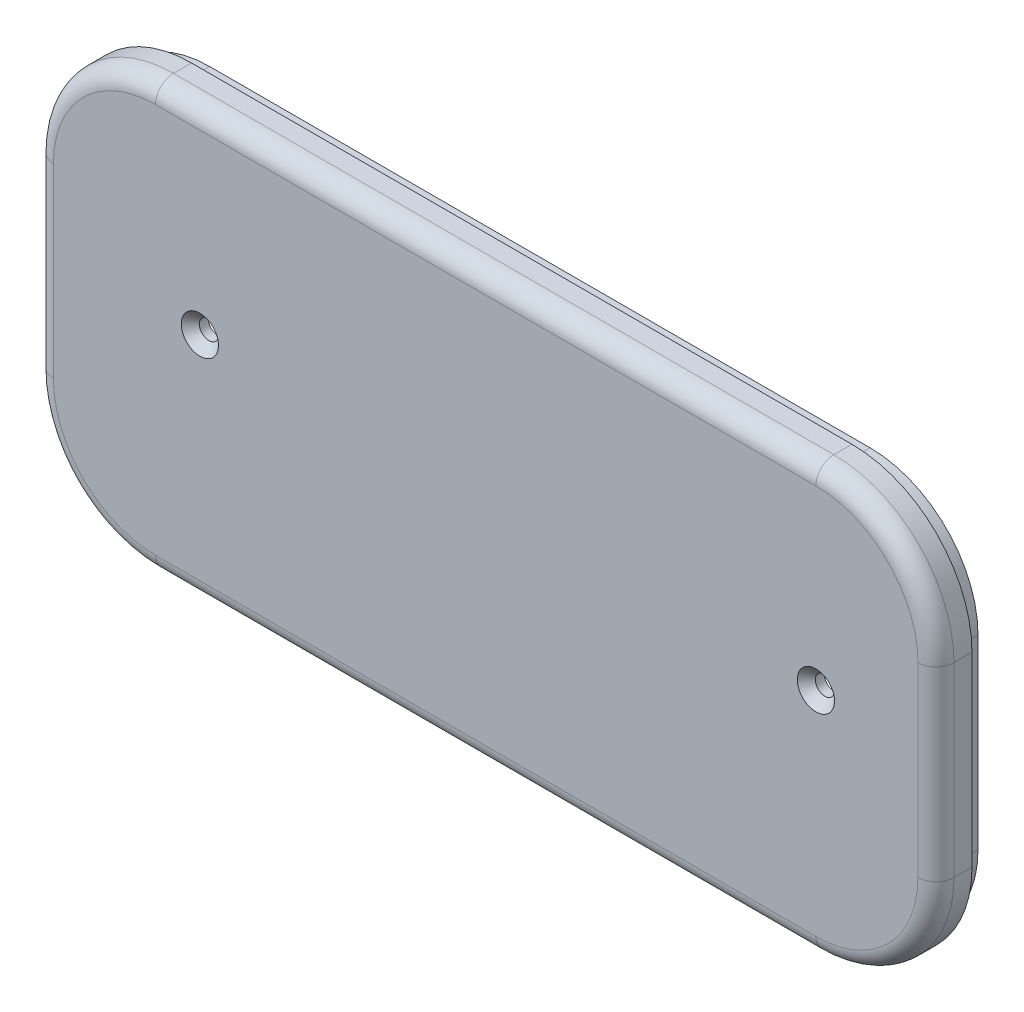
SolidWorks part; units mm, degrees
ref_plane "Front Plane" through (0, 0, 0) normal (0, 0, 1) x (1, 0, 0)
ref_plane "Top Plane" through (0, 0, 0) normal (0, 1, 0) x (1, 0, 0)
ref_plane "Right Plane" through (0, 0, 0) normal (1, 0, 0) x (0, 0, -1)
sketch "Sketch1" plane through (0, 0, 0) normal (0, 0, 1) x (1, 0, 0)
  line L8 (67.5, -46) -> (67.5, -15)
  line L9 (47.5, 5) -> (-62.5, 5)
  line L10 (-82.5, -15) -> (-82.5, -46)
  line L11 (-62.5, -66) -> (47.5, -66)
  arc A8 (47.5, -66) -> (67.5, -46) centre (47.5, -46) ccw
  arc A9 (67.5, -15) -> (47.5, 5) centre (47.5, -15) ccw
  arc A10 (-62.5, 5) -> (-82.5, -15) centre (-62.5, -15) ccw
  arc A11 (-82.5, -46) -> (-62.5, -66) centre (-62.5, -46) ccw
extrude "Boss-Extrude1" add sketch "Sketch1" along normal blind 3
sketch "Sketch2" plane through (0, 0, 0) normal (0, 0, -1) x (-1, 0, 0)
  line L0 (-47.5, -64) -> (62.5, -64)
  line L1 (80.5, -46) -> (80.5, -15)
  line L2 (62.5, 3) -> (-47.5, 3)
  line L3 (-65.5, -15) -> (-65.5, -46)
  line L4 (-47.5, -66) -> (62.5, -66)
  line L5 (82.5, -46) -> (82.5, -15)
  line L6 (62.5, 5) -> (-47.5, 5)
  line L7 (-67.5, -15) -> (-67.5, -46)
  line L8 (-47.5, -66) -> (62.5, -66)
  line L9 (82.5, -46) -> (82.5, -15)
  line L10 (62.5, 5) -> (-47.5, 5)
  line L11 (-67.5, -15) -> (-67.5, -46)
  arc A0 (62.5, -64) -> (80.5, -46) centre (62.5, -46) ccw
  arc A1 (80.5, -15) -> (62.5, 3) centre (62.5, -15) ccw
  arc A2 (-47.5, 3) -> (-65.5, -15) centre (-47.5, -15) ccw
  arc A3 (-65.5, -46) -> (-47.5, -64) centre (-47.5, -46) ccw
  arc A4 (-67.5, -46) -> (-47.5, -66) centre (-47.5, -46) ccw
  arc A5 (62.5, -66) -> (82.5, -46) centre (62.5, -46) ccw
  arc A6 (82.5, -15) -> (62.5, 5) centre (62.5, -15) ccw
  arc A7 (-47.5, 5) -> (-67.5, -15) centre (-47.5, -15) ccw
  arc A8 (-67.5, -46) -> (-47.5, -66) centre (-47.5, -46) ccw
  arc A9 (62.5, -66) -> (82.5, -46) centre (62.5, -46) ccw
  arc A10 (82.5, -15) -> (62.5, 5) centre (62.5, -15) ccw
  arc A11 (-47.5, 5) -> (-67.5, -15) centre (-47.5, -15) ccw
  dimension "D1" = 0
  dimension "D2" = 2
extrude "Boss-Extrude2" add sketch "Sketch2" along normal blind 3
fillet "Fillet1" radius 3 8 edges at (-7.5, -66, 3) (-76.6421, -60.1421, 3) (-82.5, -30.5, 3) (-76.6421, -0.8579, 3) (-7.5, 5, 3) (61.6421, -0.8579, 3) (67.5, -30.5, 3) (61.6421, -60.1421, 3)
sketch "Sketch3" plane through (0, 0, 0) normal (0, 0, -1) x (-1, 0, 0)
  line L0 (-62.5, -15) -> (-62.5, -46)
  line L1 (-47.5, -61) -> (62.5, -61)
  line L2 (77.5, -46) -> (77.5, -15)
  line L3 (62.5, 0) -> (-47.5, 0)
  line L4 (-65.5, -15) -> (-65.5, -46)
  line L5 (-47.5, -64) -> (62.5, -64)
  line L6 (80.5, -46) -> (80.5, -15)
  line L7 (62.5, 3) -> (-47.5, 3)
  line L8 (-65.5, -15) -> (-65.5, -46)
  line L9 (-47.5, -64) -> (62.5, -64)
  line L10 (80.5, -46) -> (80.5, -15)
  line L11 (62.5, 3) -> (-47.5, 3)
  arc A0 (-62.5, -46) -> (-47.5, -61) centre (-47.5, -46) ccw
  arc A1 (62.5, -61) -> (77.5, -46) centre (62.5, -46) ccw
  arc A2 (77.5, -15) -> (62.5, 0) centre (62.5, -15) ccw
  arc A3 (-47.5, 0) -> (-62.5, -15) centre (-47.5, -15) ccw
  arc A4 (-65.5, -46) -> (-47.5, -64) centre (-47.5, -46) ccw
  arc A5 (62.5, -64) -> (80.5, -46) centre (62.5, -46) ccw
  arc A6 (80.5, -15) -> (62.5, 3) centre (62.5, -15) ccw
  arc A7 (-47.5, 3) -> (-65.5, -15) centre (-47.5, -15) ccw
  arc A8 (-65.5, -46) -> (-47.5, -64) centre (-47.5, -46) ccw
  arc A9 (62.5, -64) -> (80.5, -46) centre (62.5, -46) ccw
  arc A10 (80.5, -15) -> (62.5, 3) centre (62.5, -15) ccw
  arc A11 (-47.5, 3) -> (-65.5, -15) centre (-47.5, -15) ccw
  dimension "D1" = 0
  dimension "D2" = 3
extrude "Boss-Extrude3" add sketch "Sketch3" along normal blind 6
sketch "Sketch4" plane through (0, 0, 0) normal (0, 0, -1) x (-1, 0, 0)
  circle A0 centre (-47.5, -27.5) radius 1.6
  circle A1 centre (55.1, -27.5) radius 1.6
extrude "Cut-Extrude1" cut sketch "Sketch4" against normal up to surface (3 mm away) up to face at (-7.5, -30.5, 3)
chamfer "Chamfer1" distance 1.5 angle 45 2 edges at (49.1, -27.5, 3) (-53.5, -27.5, 3)
